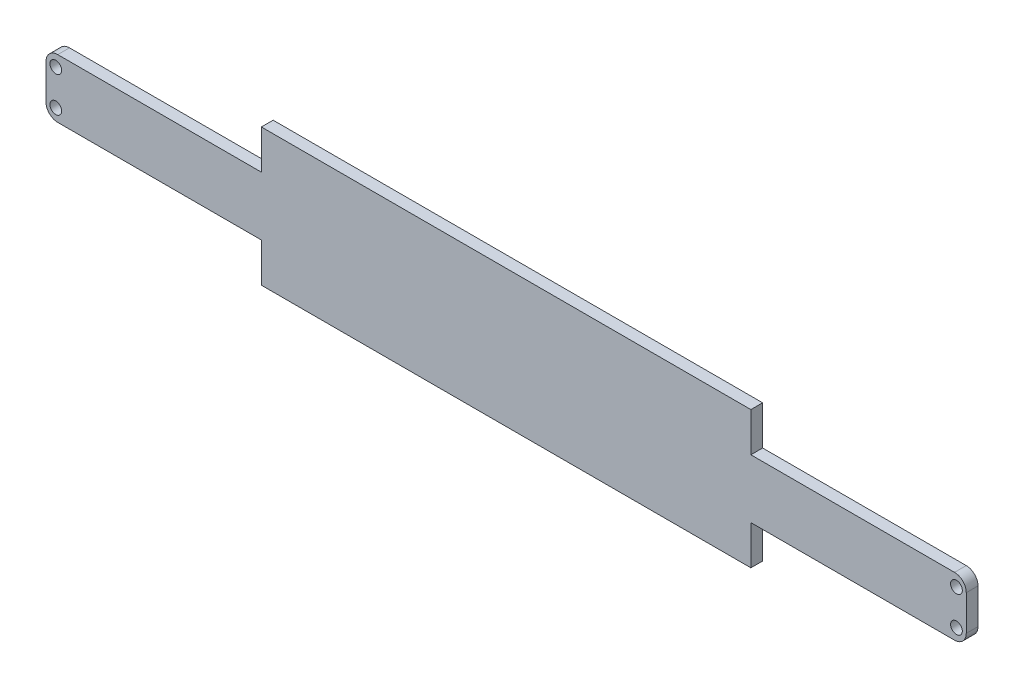
SolidWorks part; units mm, degrees
material "A2017"
ref_plane "正面" through (0, 0, 0) normal (0, 0, 1) x (1, 0, 0)
ref_plane "平面" through (0, 0, 0) normal (0, 1, 0) x (1, 0, 0)
ref_plane "右側面" through (0, 0, 0) normal (1, 0, 0) x (0, 0, -1)
sketch "ｽｹｯﾁ1" plane through (0, 0, 0) normal (0, 0, 1) x (1, 0, 0)
  line L1 (-117.5, -7.5) -> (117.5, -7.5)
  line L2 (-117.5, -7.5) -> (-117.5, 7.5)
  line L3 (-117.5, 7.5) -> (117.5, 7.5)
  line L4 (117.5, -7.5) -> (117.5, 7.5)
  line L5 (-117.5, -7.5) -> (117.5, 7.5) construction
  line L6 (-117.5, 7.5) -> (117.5, -7.5) construction
  point P0 (0, 0)
  dimension "D1" = 235
  dimension "D2" = 15
extrude "ﾎﾞｽ - 押し出し1" add sketch "ｽｹｯﾁ1" along normal blind 3
sketch "ｽｹｯﾁ2" plane through (0, 0, 3) normal (0, 0, 1) x (1, 0, 0)
  line L0 (117.5, 7.5) -> (-117.5, 7.5) construction
  line L1 (117.5, -7.5) -> (117.5, 7.5) construction
  line L2 (117.5, 0) -> (0, 0) construction
  line L3 (0, 0) -> (0, 7.5) construction
  circle A0 centre (115, 4.5) radius 1.5
  circle A1 centre (115, -4.5) radius 1.5
  circle A2 centre (-115, -4.5) radius 1.5
  circle A3 centre (-115, 4.5) radius 1.5
  dimension "D1" = 3
  dimension "D3" = 3
  dimension "D2" = 2.5
extrude "ｶｯﾄ - 押し出し1" cut sketch "ｽｹｯﾁ2" against normal through all
fillet "ﾌｨﾚｯﾄ2" radius 3 4 edges at (-117.5, 7.5, 1.5) (-117.5, -7.5, 1.5) (117.5, -7.5, 1.5) (117.5, 7.5, 1.5)
sketch "ｽｹｯﾁ6" plane through (0, 0, 0) normal (0, 0, -1) x (-1, 0, 0)
  line L1 (-62.5, -17.5) -> (62.5, -17.5)
  line L2 (-62.5, -17.5) -> (-62.5, 17.5)
  line L3 (-62.5, 17.5) -> (62.5, 17.5)
  line L4 (62.5, -17.5) -> (62.5, 17.5)
  line L5 (-62.5, -17.5) -> (62.5, 17.5) construction
  line L6 (-62.5, 17.5) -> (62.5, -17.5) construction
  point P0 (0, 0)
  dimension "D1" = 125
  dimension "D2" = 35
extrude "ﾎﾞｽ - 押し出し3" add sketch "ｽｹｯﾁ6" against normal up to surface (3 mm away) up to face at (-116.5, 4.5, 3)
